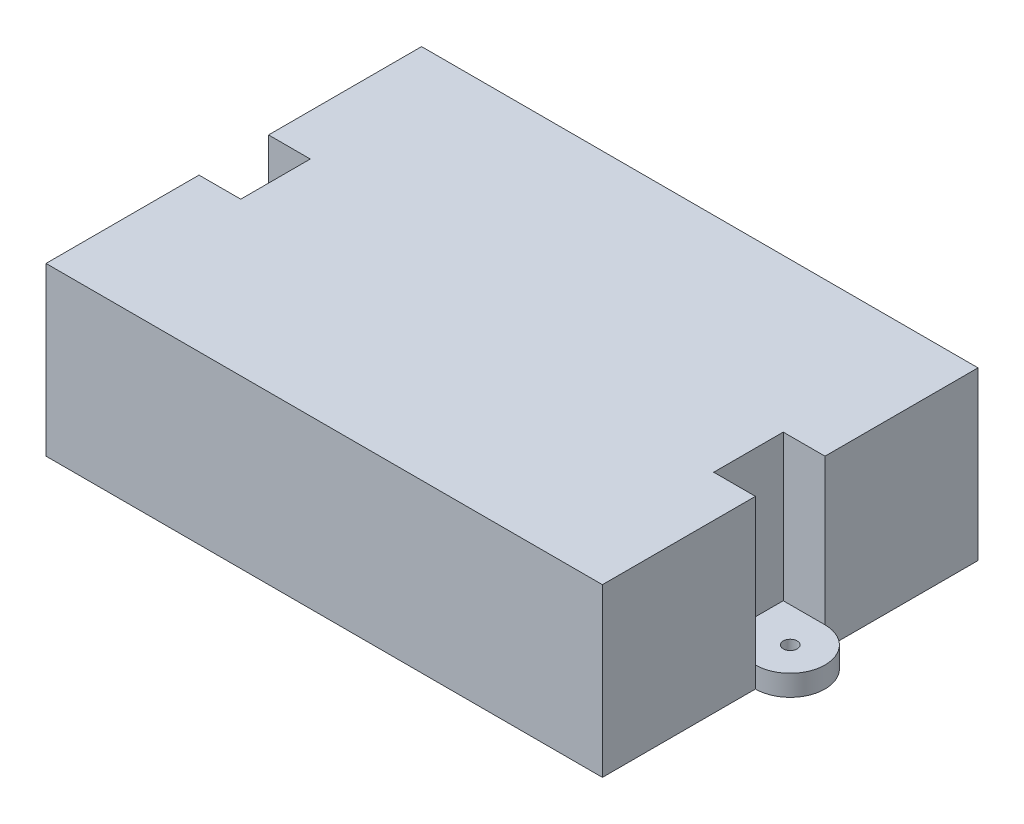
SolidWorks part; units mm, degrees
ref_plane "Front Plane" through (0, 0, 0) normal (0, 0, 1) x (1, 0, 0)
ref_plane "Top Plane" through (0, 0, 0) normal (0, 1, 0) x (1, 0, 0)
ref_plane "Right Plane" through (0, 0, 0) normal (1, 0, 0) x (0, 0, -1)
sketch "Sketch1" plane through (0, 0, 0) normal (0, 1, 0) x (1, 0, 0)
  line L0 (-40, 5) -> (-40, 27)
  line L1 (-40, -27) -> (40, -27)
  line L2 (-40, -27) -> (-40, -5)
  line L3 (-40, 27) -> (40, 27)
  line L4 (40, -27) -> (40, -5)
  line L5 (-40, -27) -> (40, 27) construction
  line L6 (-40, 27) -> (40, -27) construction
  line L7 (40, 5) -> (40, 27)
  arc A0 (40, -5) -> (40, 5) centre (40, 0) ccw
  arc A1 (-40, 5) -> (-40, -5) centre (-40, 0) ccw
  circle A2 centre (-40, 0) radius 1
  circle A3 centre (40, 0) radius 1
  point P0 (0, 0)
  dimension "D3" = 10
  dimension "D4" = 10
  dimension "D5" = 2
  dimension "D6" = 2
  dimension "D1" = 54
  dimension "D2" = 80
extrude "Boss-Extrude1" add sketch "Sketch1" along normal blind 3
sketch "Sketch2" plane through (0, 3, 0) normal (0, 1, 0) x (1, 0, 0)
  line L3 (-40, 5) -> (-34, 5)
  line L4 (-40, -5) -> (-34, -5)
  line L5 (-34, 5) -> (-34, -5)
  line L6 (40, 5) -> (40, 27)
  line L7 (40, 27) -> (-40, 27)
  line L8 (-40, 27) -> (-40, 5)
  line L9 (-40, -5) -> (-40, -27)
  line L10 (-40, -27) -> (40, -27)
  line L11 (40, -27) -> (40, -5)
  line L12 (40, 5) -> (40, 27)
  line L13 (40, 27) -> (-40, 27)
  line L14 (-40, 27) -> (-40, 5)
  line L15 (-40, -5) -> (-40, -27)
  line L16 (-40, -27) -> (40, -27)
  line L17 (40, -27) -> (40, -5)
  line L19 (40, 5) -> (34, 5)
  line L20 (40, -5) -> (34, -5)
  line L21 (34, 5) -> (34, -5)
  arc A2 (-40, 5) -> (-40, -5) centre (-40, 0) ccw
  arc A3 (40, -5) -> (40, 5) centre (40, 0) ccw
  dimension "D4" = 10
  dimension "D2" = 6
  dimension "D3" = 6
  dimension "D5" = 10
extrude "Boss-Extrude2" add sketch "Sketch2" along normal blind 21
equation "\"length\"= 80"
equation "\"width\"= 54"
equation "\"height\"= 24 - \"base_height\""
equation "\"D1@Sketch1\"=\"width\""
equation "\"D2@Sketch1\"=\"length\""
equation "\"D1@Boss-Extrude1\"=\"base_height\""
equation "\"hole_radius\"= 1"
equation "\"base_radius\"= 5"
equation "\"base_height\"= 3"
equation "\"indent_depth\"= 6"
equation "\"D2@Sketch2\"=\"indent_depth\""
equation "\"D3@Sketch2\"=\"indent_depth\""
equation "\"D4@Sketch2\"=\"base_radius\"*2"
equation "\"D5@Sketch2\"=\"base_radius\"*2"
equation "\"D1@Boss-Extrude2\"=\"height\""
